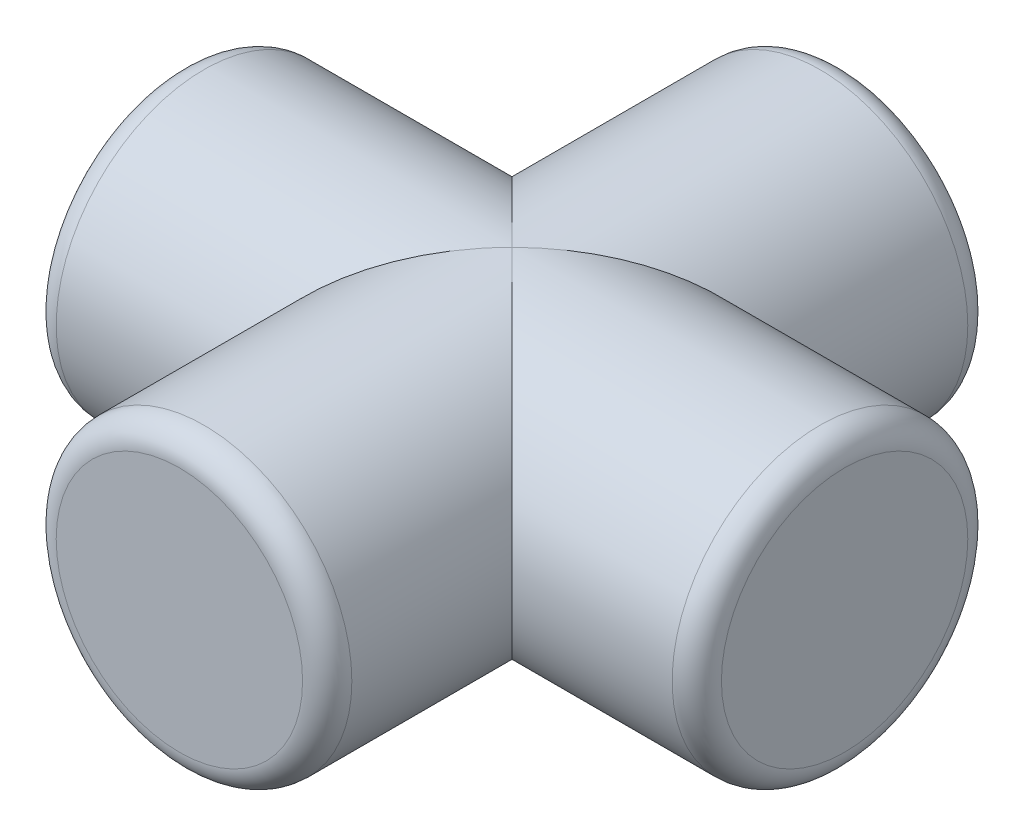
SolidWorks part; units mm, degrees
material "Cast Carbon Steel"
ref_plane "Front Plane" through (0, 0, 0) normal (0, 0, 1) x (1, 0, 0)
ref_plane "Top Plane" through (0, 0, 0) normal (0, 1, 0) x (1, 0, 0)
ref_plane "Right Plane" through (0, 0, 0) normal (1, 0, 0) x (0, 0, -1)
sketch "Sketch2" plane through (0, 0, 0) normal (0, 0, 1) x (1, 0, 0)
  circle A0 centre (0, 0) radius 7.62
extrude "Boss-Extrude1" add sketch "Sketch2" along normal blind 34.29
sketch "Sketch3" plane through (0, 0, 0) normal (1, 0, 0) x (0, 0, -1)
  circle A0 centre (-17.145, 0) radius 7.62
extrude "Boss-Extrude2" add sketch "Sketch3" along normal blind 17.145 and the other way blind 17.145
fillet "Fillet1" radius 1.27 4 edges at (7.62, 0, 34.29) (17.145, 0, 9.525) (-17.145, 0, 9.525) (7.62, 0, 0)
sketch "Sketch4" plane through (0, 0, 0) normal (0, 1, 0) x (1, 0, 0)
  point P0 (0, -17.145)
